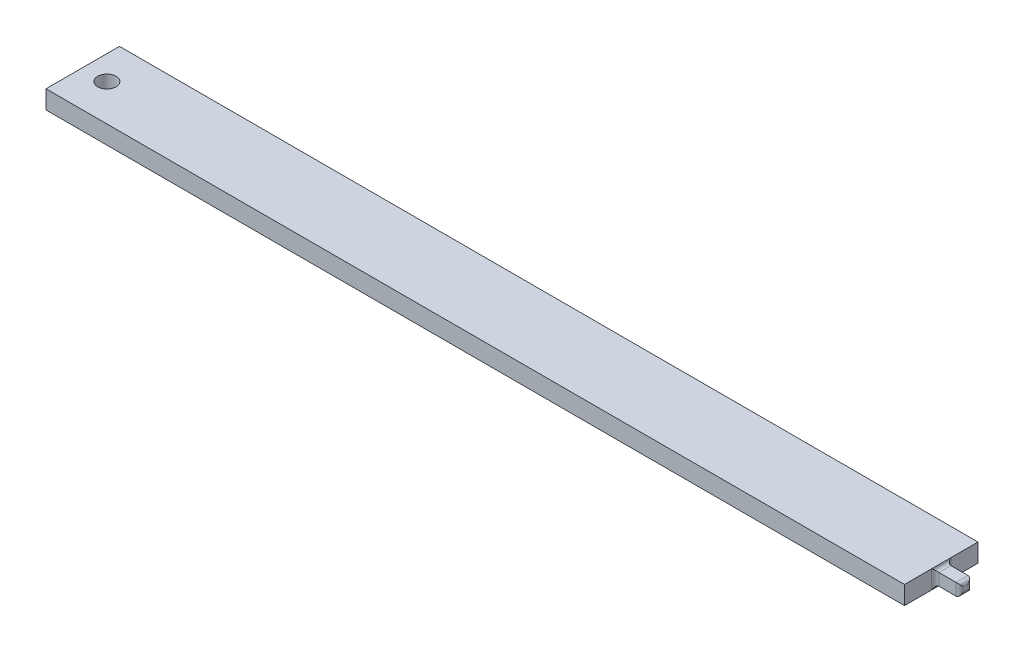
SolidWorks part; units mm, degrees
ref_plane "Front Plane" through (0, 0, 0) normal (0, 0, 1) x (1, 0, 0)
ref_plane "Top Plane" through (0, 0, 0) normal (0, 1, 0) x (1, 0, 0)
ref_plane "Right Plane" through (0, 0, 0) normal (1, 0, 0) x (0, 0, -1)
sketch "Sketch1" plane through (0, 0, 0) normal (0, 1, 0) x (1, 0, 0)
  line L1 (-140.2, -6) -> (140.2, -6)
  line L2 (-140.2, -6) -> (-140.2, 6)
  line L3 (-140.2, 6) -> (140.2, 6)
  line L4 (140.2, -6) -> (140.2, 6)
  line L5 (-140.2, -6) -> (140.2, 6) construction
  line L6 (-140.2, 6) -> (140.2, -6) construction
  point P0 (0, 0)
  dimension "D1" = 12
extrude "Boss-Extrude1" add sketch "Sketch1" along normal blind 3
sketch "Sketch3" plane through (0, 3, 0) normal (0, 1, 0) x (1, 0, 0)
  line L0 (-136.25, 0) -> (136.25, 0) construction
  circle A0 centre (-136.25, 0) radius 1.5
  circle A1 centre (136.25, 0) radius 1.5
  point P5 (0, 0)
  dimension "D1" = 1.5
  dimension "D2" = 272.5
extrude "Cut-Extrude1" cut sketch "Sketch3" against normal through all contours A1 | A0
sketch "Sketch4" plane through (0, 0, 0) normal (0, -1, 0) x (1, 0, 0)
  circle A0 centre (0, 0) radius 5
  dimension "D1" = 5
sketch "Sketch5" plane through (0, 3, 0) normal (0, 1, 0) x (1, 0, 0)
  line L0 (-140.2, 0) -> (140.2, 0) construction
  line L1 (-140.2, 6) -> (-140.2, -6) construction
  line L2 (140.2, -6) -> (140.2, 6) construction
sketch "Sketch6" plane through (0, 3, 0) normal (0, 1, 0) x (1, 0, 0)
  line L0 (-140.2, -6) -> (140.2, -6) construction
  line L1 (0, -6) -> (140.2, -6)
  line L2 (0, -6) -> (0, 6)
  line L3 (0, 6) -> (140.2, 6)
  line L4 (140.2, -6) -> (140.2, 6)
extrude "Cut-Extrude2" cut sketch "Sketch6" against normal through all
sketch "Sketch7" plane through (0, 0, 0) normal (1, 0, 0) x (0, 0, -1)
  line L1 (-0.975, 0.525) -> (0.975, 0.525)
  line L2 (-0.975, 0.525) -> (-0.975, 2.475)
  line L3 (-0.975, 2.475) -> (0.975, 2.475)
  line L4 (0.975, 0.525) -> (0.975, 2.475)
  line L5 (-0.975, 0.525) -> (0.975, 2.475) construction
  line L6 (-0.975, 2.475) -> (0.975, 0.525) construction
  point P0 (0, 1.5)
  dimension "D1" = 1.95
extrude "Boss-Extrude2" add sketch "Sketch7" along normal blind 4
fillet "Fillet1" radius 0.6 8 edges at (4, 0.525, 0) (4, 1.5, 0.975) (4, 2.475, 0) (4, 1.5, -0.975) (0, 1.5, -0.975) (0, 1.5, 0.975) (0, 2.475, 0) (0, 0.525, 0)
